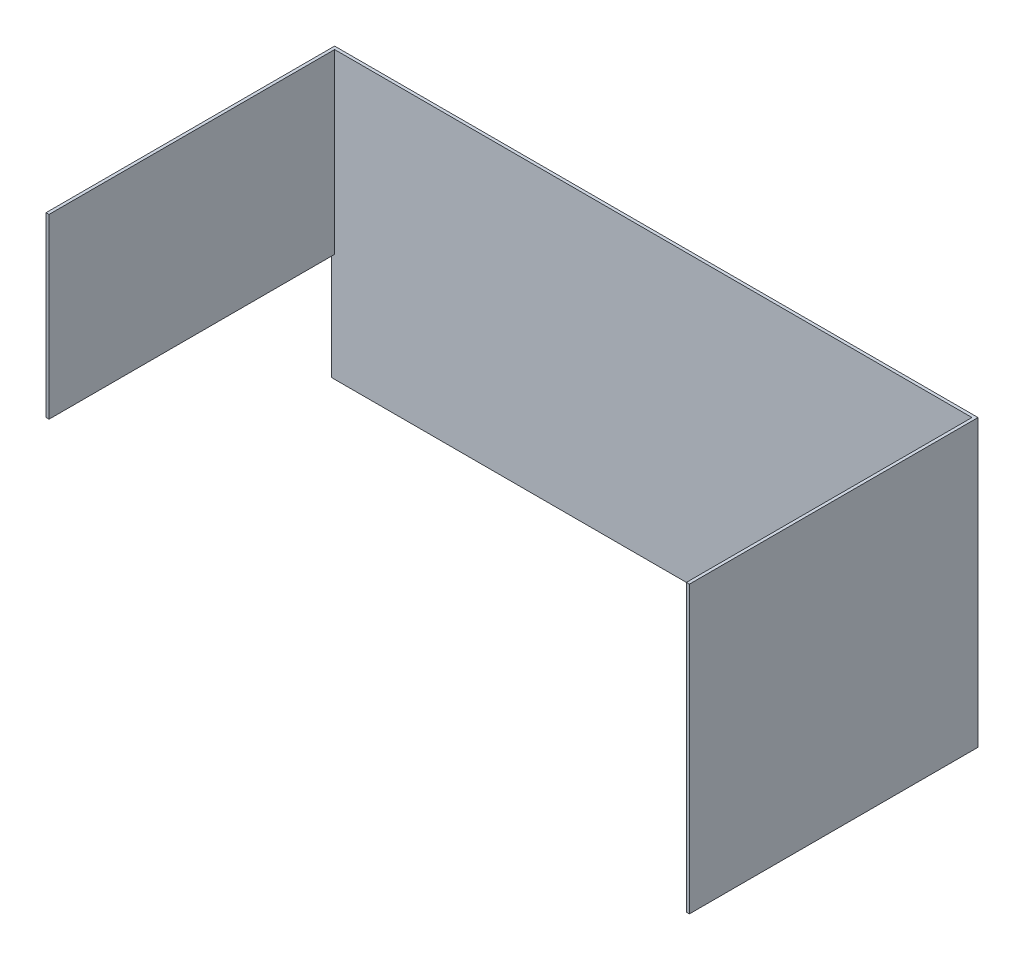
SolidWorks part; units mm, degrees
ref_plane "Front Plane" through (0, 0, 0) normal (0, 0, 1) x (1, 0, 0)
ref_plane "Top Plane" through (0, 0, 0) normal (0, 1, 0) x (1, 0, 0)
ref_plane "Right Plane" through (0, 0, 0) normal (1, 0, 0) x (0, 0, -1)
sketch "Sketch1" plane through (0, 0, 0) normal (0, 1, 0) x (1, 0, 0)
  line L2 (-339.725, -152.4) -> (-339.725, 152.4)
  line L3 (-339.725, 152.4) -> (339.725, 152.4)
  line L4 (339.725, -152.4) -> (339.725, 152.4)
  line L5 (-339.725, -152.4) -> (339.725, 152.4) construction
  line L6 (-339.725, 152.4) -> (339.725, -152.4) construction
  point P0 (0, 0)
  dimension "D1" = 679.45
  dimension "D2" = 304.8
extrude "Extrude-Thin1" add sketch "Sketch1" along normal blind 301.625 thin thin type one direction reverse wall 3.175
sketch "Sketch2" plane through (-336.55, 0, 0) normal (1, 0, 0) x (0, 0, -1)
  line L0 (-152.4, 114.3) -> (149.225, 114.3)
  line L1 (-152.4, 301.625) -> (-152.4, 0) construction
  line L2 (149.225, 301.625) -> (149.225, 0) construction
  line L3 (149.225, 114.3) -> (149.225, 0)
  line L4 (149.225, 0) -> (-152.4, 0)
  line L5 (-152.4, 0) -> (-152.4, 114.3)
  dimension "D1" = 114.3
extrude "Cut-Extrude1" cut sketch "Sketch2" against normal up to next
